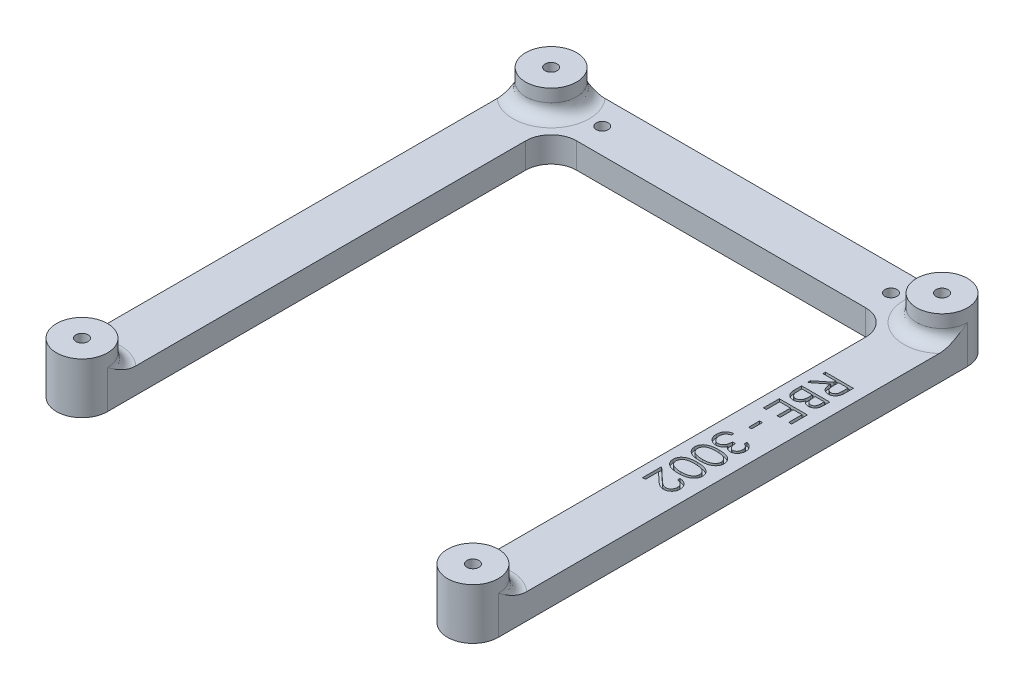
SolidWorks part; units mm, degrees
ref_plane "Front Plane" through (0, 0, 0) normal (0, 0, 1) x (1, 0, 0)
ref_plane "Top Plane" through (0, 0, 0) normal (0, 1, 0) x (1, 0, 0)
ref_plane "Right Plane" through (0, 0, 0) normal (1, 0, 0) x (0, 0, -1)
sketch "Sketch1" plane through (0, 0, 0) normal (0, 1, 0) x (1, 0, 0)
  line L0 (-27.55, 32.425) -> (27.55, 32.425)
  line L1 (-24.375, -29.25) -> (-21.2, -29.25) construction
  line L2 (-24.375, -29.25) -> (-24.375, 29.25) construction
  line L3 (-24.375, 29.25) -> (24.375, 29.25) construction
  line L4 (24.375, -29.25) -> (24.375, 29.25) construction
  line L5 (-24.375, -29.25) -> (-21.2, -25.44) construction
  line L6 (-24.375, 29.25) -> (21.7292, -26.075) construction
  line L7 (27.55, -32.425) -> (27.55, 32.425)
  line L8 (-27.55, -32.425) -> (-21.2, -32.425)
  line L9 (-27.55, -32.425) -> (-27.55, 32.425)
  line L10 (-21.2, 26.075) -> (21.2, 26.075)
  line L11 (21.2, -26.075) -> (21.2, 26.075)
  line L12 (-21.2, -26.075) -> (-21.7292, -26.075) construction
  line L13 (-21.2, -26.075) -> (-21.2, 26.075)
  line L14 (-21.2, -26.075) -> (-21.2, -32.425)
  line L15 (21.2, -26.075) -> (21.2, -32.425)
  line L16 (-21.7292, -26.075) -> (21.7292, -26.075) construction
  line L17 (21.7292, -26.075) -> (21.2, -26.075) construction
  line L18 (-21.2, -26.075) -> (21.2, -26.075) construction
  line L19 (-21.2, -29.25) -> (21.2, -29.25) construction
  line L20 (21.2, -29.25) -> (24.375, -29.25) construction
  line L21 (-24.375, -29.25) -> (24.375, -29.25) construction
  line L22 (-21.2, -32.425) -> (21.2, -32.425) construction
  line L23 (21.2, -32.425) -> (27.55, -32.425)
  line L24 (-27.55, -32.425) -> (27.55, -32.425) construction
  line L25 (-21.7292, -26.075) -> (0, 0) construction
  line L26 (0, 0) -> (24.375, 29.25) construction
  line L27 (-21.2, -25.44) -> (-21.7292, -26.075) construction
  line L28 (21.7292, -26.075) -> (21.2, -25.44) construction
  line L29 (21.2, -25.44) -> (24.375, -29.25) construction
  circle A0 centre (-24.375, 29.25) radius 0.75
  circle A1 centre (24.375, 29.25) radius 0.75
  circle A2 centre (24.375, -29.25) radius 0.75
  circle A3 centre (-24.375, -29.25) radius 0.75
  point P0 (0, 0)
  dimension "D3" = 1.5
  dimension "D1" = 48.75
  dimension "D2" = 58.5
  dimension "D4" = 3.175
  dimension "D5" = 3.175
extrude "Boss-Extrude1" add sketch "Sketch1" along normal blind 3.175
fillet "Fillet1" radius 3.175 8 edges at (21.2, 1.5875, -26.075) (-21.2, 1.5875, -26.075) (-27.55, 1.5875, -32.425) (27.55, 1.5875, -32.425) (-27.55, 1.5875, 32.425) (27.55, 1.5875, 32.425) (21.2, 1.5875, 32.425) (-21.2, 1.5875, 32.425)
sketch "Sketch2" plane through (0, 3.175, 0) normal (0, 1, 0) x (1, 0, 0)
  circle A0 centre (-24.375, 29.25) radius 0.75 construction
  circle A1 centre (-24.375, 29.25) radius 0.75
  circle A2 centre (-24.375, 29.25) radius 3.175
  arc A3 (-24.375, 32.425) -> (-27.55, 29.25) centre (-24.375, 29.25) ccw construction
extrude "Boss-Extrude2" add sketch "Sketch2" along normal blind 3.175
mirror "Mirror3" about plane through (0, 0, 0) normal (1, 0, 0) of "Boss-Extrude2"
mirror "Mirror4" about plane through (0, 0, 0) normal (0, 0, 1) of "Mirror3", "Boss-Extrude2"
fillet "Fillet2" radius 1.5875 4 edges at (-22.1299, 3.175, -27.0049) (-24.375, 3.175, 26.075) (22.1299, 3.175, -27.0049) (24.375, 3.175, 26.075)
sketch "Sketch3" plane through (0, 3.175, 0) normal (0, 1, 0) x (1, 0, 0)
  line L0 (-18, 29.25) -> (18, 29.25) construction
  line L1 (0, 32.425) -> (0, 26.075) construction
  line L2 (20.8252, 32.425) -> (-20.8252, 32.425) construction
  line L3 (-18.025, 26.075) -> (18.025, 26.075) construction
  circle A0 centre (18, 29.25) radius 0.75
  circle A1 centre (-18, 29.25) radius 0.75
  point P10 (0, 29.25)
  point P11 (0, 29.25)
  dimension "D2" = 1.5
  dimension "D1" = 36
extrude "Cut-Extrude1" cut sketch "Sketch3" against normal through all both and the other way through all
sketch "Sketch4" plane through (0, 3.175, 0) normal (0, 1, 0) x (1, 0, 0)
  line L0 (22.4653, 17.0568) -> (22.4653, -16.1912) construction
  text T0 "RBE - 3002"
extrude "Cut-Extrude2" cut sketch "Sketch4" against normal blind 0.4
